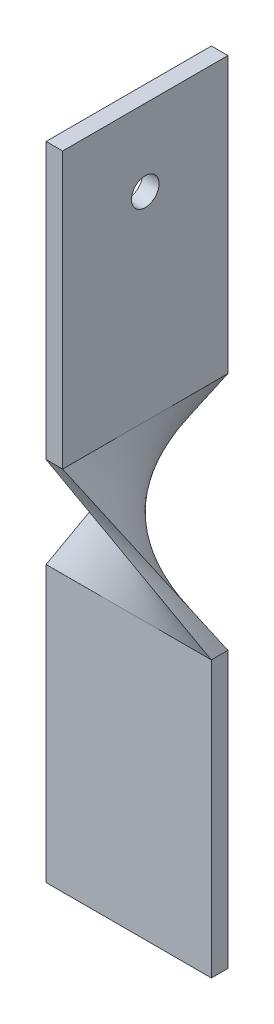
SolidWorks part; units mm, degrees
material "1060 Alloy"
ref_plane "Front Plane" through (0, 0, 0) normal (0, 0, 1) x (1, 0, 0)
ref_plane "Top Plane" through (0, 0, 0) normal (0, 1, 0) x (1, 0, 0)
ref_plane "Right Plane" through (0, 0, 0) normal (1, 0, 0) x (0, 0, -1)
sketch "Sketch1" plane through (0, 0, 0) normal (0, 1, 0) x (1, 0, 0)
  line L1 (0, 0) -> (30, 0)
  line L2 (0, 0) -> (0, 3)
  line L3 (0, 3) -> (30, 3)
  line L4 (30, 0) -> (30, 3)
  dimension "D1" = 30
  dimension "D2" = 3
extrude "Boss-Extrude1" add sketch "Sketch1" along normal blind 50
sketch "Sketch2" plane through (0, 50, 0) normal (0, 1, 0) x (1, 0, 0)
  line L0 (0, 3) -> (0, 0) construction
  line L1 (13.5, 16.5) -> (16.5, 16.5)
  line L2 (13.5, 16.5) -> (13.5, -13.5)
  line L3 (13.5, -13.5) -> (16.5, -13.5)
  line L4 (16.5, 16.5) -> (16.5, -13.5)
  line L6 (30, 3) -> (0, 3) construction
  point P6 (0, 1.5)
  point P7 (13.5, 1.5)
  point P10 (15, 3)
  point P11 (15, 16.5)
  dimension "D1" = 3
  dimension "D2" = 30
extrude "Boss-Extrude2" add sketch "Sketch2" along normal blind 50 from offset 30 separate body
loft "Loft1" add section face at (15, 50, -1.5) section face at (15, 80, -1.5) connector at (0, 50, -3) connector at (16.5, 80, -16.5)
sketch "Sketch3" plane through (13.5, 0, 0) normal (-1, 0, 0) x (0, 0, 1)
  line L0 (-16.5, 130) -> (13.5, 130) construction
  circle A0 centre (-1.5, 116.1121) radius 2.5
  point P5 (-1.5, 130)
  dimension "D1" = 5
extrude "Cut-Extrude1" cut sketch "Sketch3" against normal blind 50
